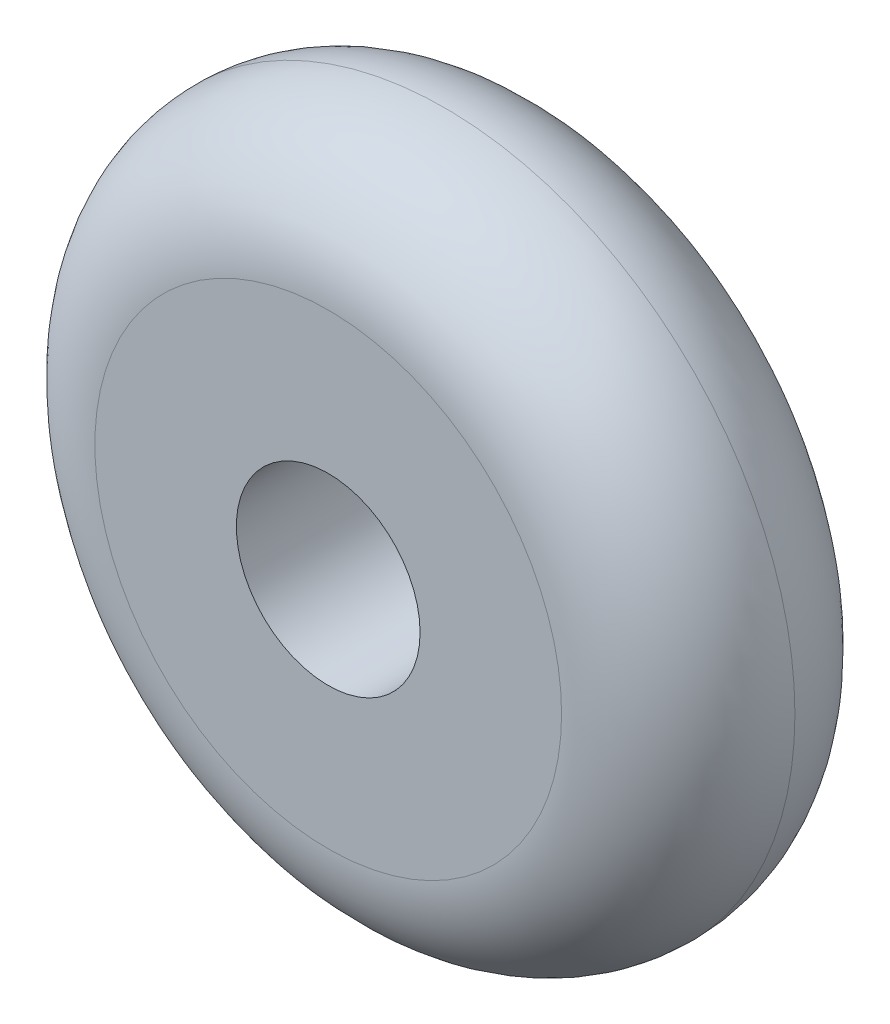
SolidWorks part; units mm, degrees
ref_plane "Front Plane" through (0, 0, 0) normal (0, 0, 1) x (1, 0, 0)
ref_plane "Top Plane" through (0, 0, 0) normal (0, 1, 0) x (1, 0, 0)
ref_plane "Right Plane" through (0, 0, 0) normal (1, 0, 0) x (0, 0, -1)
sketch "Sketch1" plane through (0, 0, 0) normal (0, 0, 1) x (1, 0, 0)
  circle A0 centre (0, 0) radius 38.1
  dimension "D1" = 76.2
extrude "Boss-Extrude1" add sketch "Sketch1" along normal mid plane 25.4
fillet "Fillet1" radius 12.7 2 edges at (38.1, 0, -12.7) (38.1, 0, 12.7)
sketch "Sketch2" plane through (0, 0, 12.7) normal (0, 0, 1) x (1, 0, 0)
  circle A0 centre (0, 0) radius 10
  dimension "D1" = 20
extrude "Cut-Extrude1" cut sketch "Sketch2" against normal through all both and the other way through all
sketch "Sketch3" plane through (0, 0, 0) normal (0, 0, 1) x (1, 0, 0)
  line L0 (0, -38.1) -> (-67.6263, -38.1) construction
  line L1 (0, -38.1) -> (52.0283, -38.1) construction
  circle A0 centre (0, 0) radius 38.1 construction
equation "\"D1@Sketch1\"= \"Wheel Diameter\""
equation "\"D1@Boss-Extrude1\"=\"Wheel Thickness\""
equation "\"D1@Sketch2\"=\"Wheel Cutout Diameter\""
equation "\"Wheel Thickness\"= 1in"
equation "\"Wheel Diameter\"= 3in"
equation "\"Motor Rear Diameter\" = 36.2mm"
equation "\"Motor Front Diameter\" = 12mm"
equation "\"Material Thickness\" = .25in"
equation "\"Wheel Cutout Diameter\"= 2cm"
equation "\"Motor Mount Tab Thickness\" = 100mm"
equation "\"Motor Mount Tab Height\" = 40mm"
